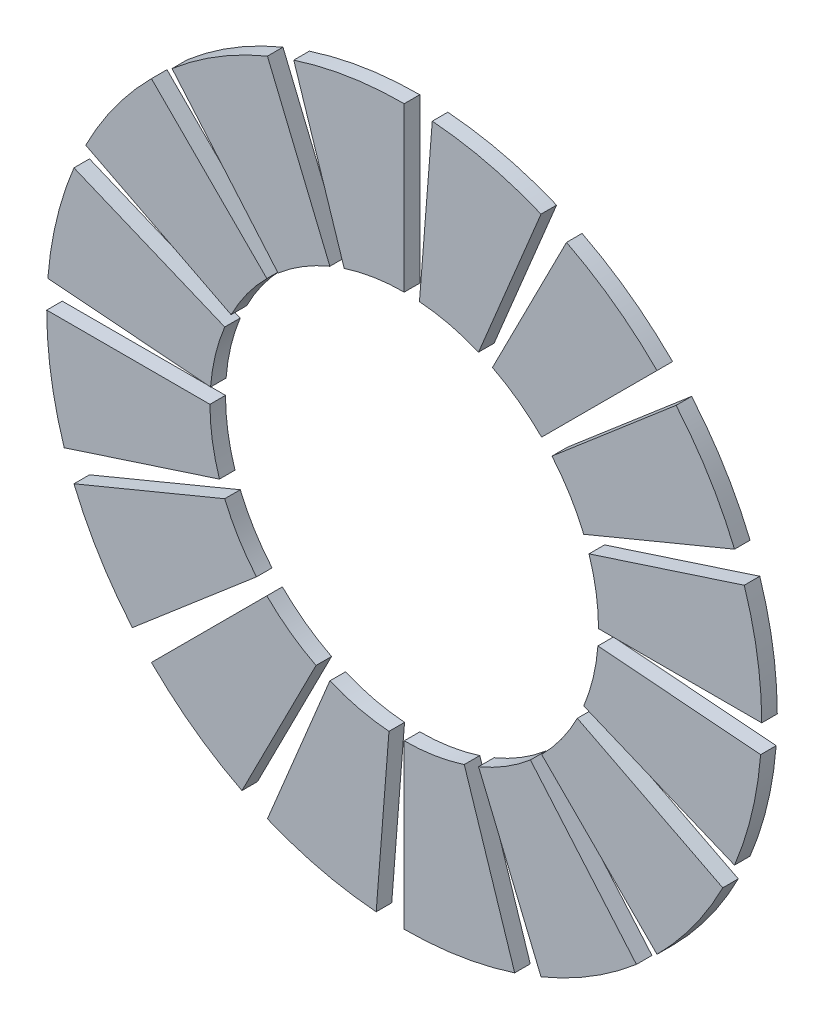
SolidWorks part; units mm, degrees
material "NdFeB"
ref_plane "Ön Düzlem" through (0, 0, 0) normal (0, 0, 1) x (1, 0, 0)
ref_plane "Üst Düzlem" through (0, 0, 0) normal (0, 1, 0) x (1, 0, 0)
ref_plane "Sağ Düzlem" through (0, 0, 0) normal (1, 0, 0) x (0, 0, -1)
sketch "Sketch2" plane through (0, 0, 0) normal (0, 0, 1) x (1, 0, 0)
  line L0 (0, 0) -> (46, 0) construction
  line L1 (0, 0) -> (43.7486, 14.2148) construction
  line L2 (25, 0) -> (46, 0)
  line L3 (23.7764, 7.7254) -> (43.7486, 14.2148)
  circle A0 centre (0, 0) radius 25 construction
  circle A1 centre (0, 0) radius 46 construction
  arc A2 (25, 0) -> (23.7764, 7.7254) centre (0, 0) ccw
  arc A3 (46, 0) -> (43.7486, 14.2148) centre (0, 0) ccw
  point P70 (0, 0)
  dimension "D1" = 50
  dimension "D2" = 92
  dimension "D3" = 18
extrude "Boss-Extrude2" add sketch "Sketch2" along normal blind 2
pattern_circular "CirPattern12" count 16 over 360 about axis through (0, 0, 2) along (0, 0, 1) of bodies 147
